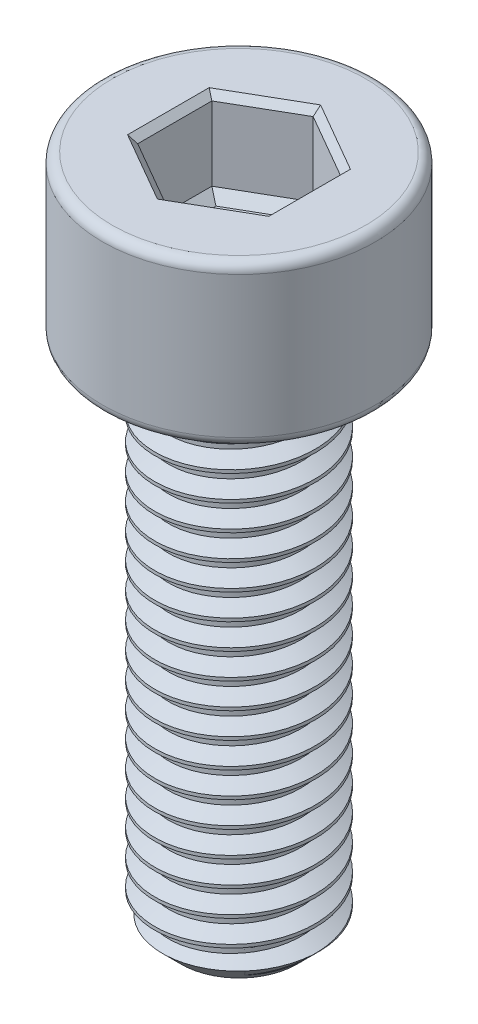
SolidWorks part; units mm, degrees
material "AISI Type A2 Tool Steel"
ref_plane "Front Plane" through (0, 0, 0) normal (0, 0, 1) x (1, 0, 0)
ref_plane "Top Plane" through (0, 0, 0) normal (0, 1, 0) x (1, 0, 0)
ref_plane "Right Plane" through (0, 0, 0) normal (1, 0, 0) x (0, 0, -1)
sketch "Sketch1" plane through (0, 0, 0) normal (0, 1, 0) x (1, 0, 0)
  circle A0 centre (0, 0) radius 2.5
  dimension "D1" = 5
extrude "Boss-Extrude1" add sketch "Sketch1" along normal blind 16
thread "Thread1" pitch 0.8 method cut profile "Thread Profile1" start angle 0, offset 1, length 0, pitch 0.8, diameter 5
ref_plane "Plane1" through (-2.5, 17, 0) normal (0, 0, 1) x (-1, 0, 0)
sketch "Thread Profile1" plane through (-2.5, 17, 0) normal (0, 0, 1) x (-1, 0, 0)
  line L0 (0, 0) -> (0, 0.8) construction
  line L11 (0, 0) -> (0, 0.7)
  line L12 (0, 0.7) -> (-0.433, 0.45)
  line L13 (-0.433, 0.45) -> (-0.433, 0.25)
  line L15 (-0.433, 0.25) -> (0, 0)
  line L17 (-0.433, 0.35) -> (0, 0.35) construction
  point P2 (0, 0)
  dimension "Pitch" = 0.8
  dimension "Profile_Angle" = 60
  dimension "Profile_Land" = 0.2
  dimension "Profile_Height" = 0.433
sketch "Sketch5" plane through (0, 16, 0) normal (0, 1, 0) x (1, 0, 0)
  circle A0 centre (0, 0) radius 4.25
  dimension "D1" = 8.5
extrude "Boss-Extrude2" add sketch "Sketch5" along normal blind 5
fillet "Fillet1" radius 0.3 2 edges at (0, 16, 4.25) (0, 21, 4.25)
sketch "Sketch6" plane through (0, 0, 0) normal (0, 0, 1) x (1, 0, 0)
  line L0 (0, 0) -> (0, 0.2882) construction
  line L1 (0, 0) -> (2.51, 0) construction
  line L2 (2.51, 0) -> (2.51, 0.7)
  line L3 (2.51, 0.7) -> (1.81, 0)
  line L4 (1.81, 0) -> (2.51, 0)
  dimension "D1" = 45
  dimension "D2" = 0.7
  dimension "D3" = 2.51
revolve "Cut-Revolve1" cut sketch "Sketch6" angle 360 about L0
sketch "Sketch7" plane through (0, 21, 0) normal (0, 1, 0) x (1, 0, 0)
  line L1 (0, 2.3094) -> (-2, 1.1547)
  line L2 (-2, 1.1547) -> (-2, -1.1547)
  line L3 (-2, -1.1547) -> (0, -2.3094)
  line L4 (0, -2.3094) -> (2, -1.1547)
  line L5 (2, -1.1547) -> (2, 1.1547)
  line L6 (2, 1.1547) -> (0, 2.3094)
  circle A0 centre (0, 0) radius 2 construction
  dimension "D1" = 4
extrude "Cut-Extrude1" cut sketch "Sketch7" against normal blind 2.5
chamfer "Chamfer1" distance 0.2 angle 45 6 edges at (-2, 21, 0) (-1, 21, 1.7321) (1, 21, 1.7321) (2, 21, 0) (1, 21, -1.7321) (-1, 21, -1.7321)
sketch "Sketch8" plane through (0, 18.5, 0) normal (0, 1, 0) x (1, 0, 0)
  line L1 (0, 2.3094) -> (-2, 1.1547)
  line L2 (-2, 1.1547) -> (-2, -1.1547)
  line L3 (-2, -1.1547) -> (0, -2.3094)
  line L4 (0, -2.3094) -> (2, -1.1547)
  line L5 (2, -1.1547) -> (2, 1.1547)
  line L6 (2, 1.1547) -> (0, 2.3094)
  circle A0 centre (0, 0) radius 2 construction
extrude "Cut-Extrude2" cut sketch "Sketch8" against normal blind 0.3 draft 45
